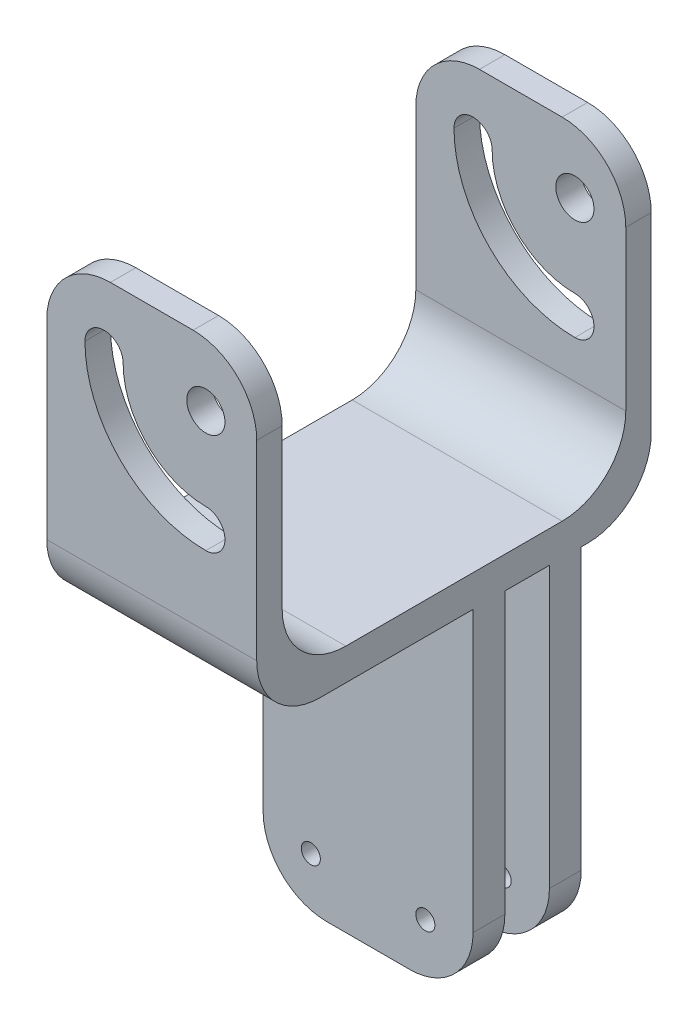
SolidWorks part; units mm, degrees
other "Marcação1"
sketch "Esboço5" plane through (0, 50, 68.25) normal (-0.797, 0.1637, 0.5813) x (0.5636, -0.1442, 0.8134)
material "Nylon - impressão"
ref_plane "Plano frontal" through (0, 0, 0) normal (0, 0, 1) x (1, 0, 0)
ref_plane "Plano superior" through (0, 0, 0) normal (0, 1, 0) x (1, 0, 0)
ref_plane "Plano direito" through (0, 0, 0) normal (1, 0, 0) x (0, 0, -1)
sketch "Esboço1" plane through (0, 0, 0) normal (0, 0, 1) x (1, 0, 0)
  line L0 (0, 0) -> (0, 50)
  line L1 (0, 50) -> (33, 50)
  line L2 (33, 50) -> (33, 0)
  line L3 (33, 0) -> (0, 0)
  line L4 (25, 40) -> (25, 37) construction
  circle A0 centre (25, 40) radius 3
  arc A2 (25, 24) -> (9, 40) centre (25, 40) cw construction
  arc A3 (6, 40) -> (25, 21) centre (25, 40) ccw
  arc A4 (12, 40) -> (25, 27) centre (25, 40) ccw
  arc A5 (12, 40) -> (6, 40) centre (9, 40) ccw
  arc A6 (25, 21) -> (25, 27) centre (25, 24) ccw
  point P10 (13.6863, 28.6863)
  dimension "D3" = 6
  dimension "D5" = 16
  dimension "D6" = 13
  dimension "D1" = 25
  dimension "D2" = 50
  dimension "D4" = 8
extrude "Ressalto-extrusão2" add sketch "Esboço1" along normal blind 62
sketch "Esboço3" plane through (0, 50, 0) normal (0, 1, 0) x (1, 0, 0)
  line L0 (0, -58) -> (33, -58)
  line L1 (0, -62) -> (0, 0) construction
  line L2 (33, -62) -> (33, 0) construction
  line L3 (33, -58) -> (33, -4)
  line L4 (33, -4) -> (0, -4)
  line L5 (0, -4) -> (0, -58)
  line L6 (33, 0) -> (0, 0) construction
  dimension "D1" = 4
  dimension "D2" = 4
extrude "Corte-extrusão1" cut sketch "Esboço3" against normal blind 45
sketch "Esboço7" plane through (0, 0, 0) normal (0, -1, 0) x (1, 0, 0)
  line L0 (0, 11) -> (33, 11)
  line L1 (33, 62) -> (33, 0) construction
  line L2 (0, 62) -> (0, 0) construction
  line L3 (33, 11) -> (33, 16)
  line L4 (33, 16) -> (0, 16)
  line L5 (0, 16) -> (0, 11)
  line L6 (0, 23) -> (33, 23)
  line L7 (33, 23) -> (33, 28)
  line L8 (33, 28) -> (0, 28)
  line L9 (0, 28) -> (0, 23)
  line L10 (33, 4) -> (0, 4) construction
  line L11 (33, 4) -> (0, 4)
  line M10 (33, 0) -> (33, 62)
  line M12 (0, 62) -> (0, 0)
  dimension "D1" = 5
  dimension "D2" = 5
  dimension "D3" = 7
  dimension "D4" = 7
extrude "Ressalto-extrusão3" add sketch "Esboço7" along normal blind 54 contours L8 L6 M10 M12 | L4 L0 M10 M12 region at (16.5, 0, 13.5) region at (16.5, 0, 25.5)
sketch "Esboço10" plane through (0, 0, 11) normal (0, 0, -1) x (-1, 0, 0)
  line L0 (0, -54) -> (-33, -54) construction
  line L3 (-7.5, -46) -> (-25.5, -46) construction
  line L4 (0, 0) -> (-33, 0) construction
  circle A5 centre (-25.5, -46) radius 1.5
  circle A6 centre (-7.5, -46) radius 1.5
  point P0 (-16.5, -46)
  point P2 (-16.5, 0)
  dimension "D7" = 3
  dimension "D8" = 3
  dimension "D2" = 8
  dimension "D10" = 18
extrude "Corte-extrusão2" cut sketch "Esboço10" against normal through all
fillet "Filete1" radius 10 12 edges at (16.5, 5, 4) (0, 50, 2) (33, 50, 2) (16.5, 5, 58) (16.5, 0, 62) (16.5, 0, 0) (0, 50, 60) (33, 50, 60) (33, -54, 13.5) (0, -54, 13.5) (33, -54, 25.5) (0, -54, 25.5)
